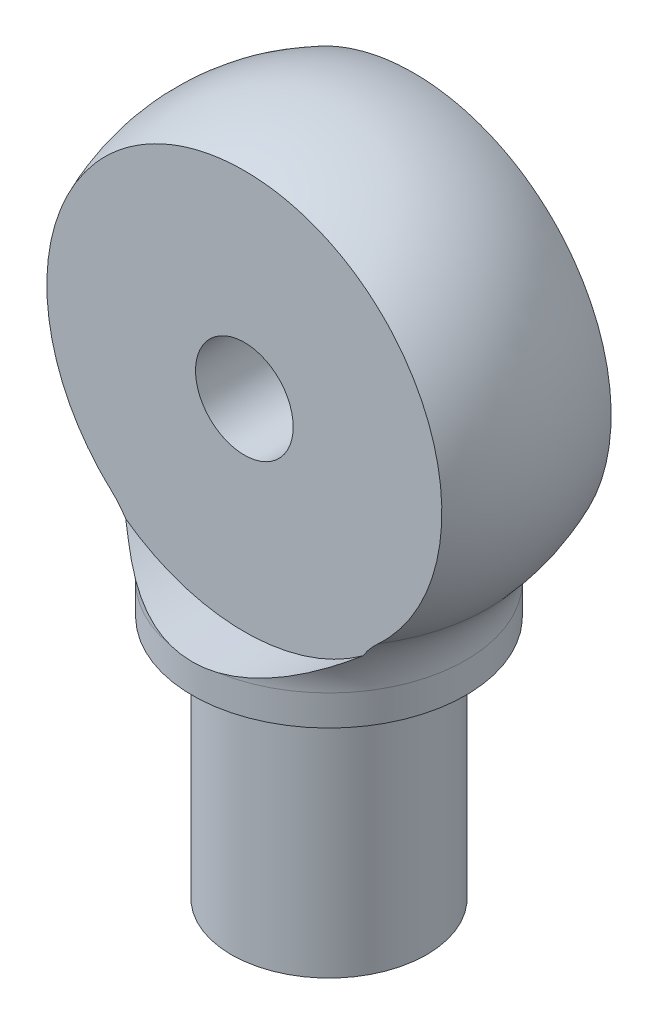
SolidWorks part; units mm, degrees
ref_plane "Front Plane" through (0, 0, 0) normal (0, 0, 1) x (1, 0, 0)
ref_plane "Top Plane" through (0, 0, 0) normal (0, 1, 0) x (1, 0, 0)
ref_plane "Right Plane" through (0, 0, 0) normal (1, 0, 0) x (0, 0, -1)
sketch "Sketch1" plane through (0, 0, 0) normal (0, 1, 0) x (1, 0, 0)
  circle A0 centre (0, 0) radius 7.62
extrude "Boss-Extrude1" add sketch "Sketch1" along normal blind 19.05
sketch "Sketch2" plane through (0, 0, 0) normal (1, 0, 0) x (0, 0, -1)
  line L0 (0, 8.382) -> (0, -8.382) construction
  line L1 (-10.668, 19.05) -> (-10.668, 24.13)
  line L2 (-10.668, 19.05) -> (0, 19.05)
  line L3 (7.62, 19.05) -> (-7.62, 19.05) construction
  line L4 (0, 19.05) -> (0, 53.8256)
  arc A0 (0, 53.8256) -> (-10.668, 24.13) centre (0, 37.0616) ccw
  dimension "D3" = 33.528
  dimension "D1" = 5.08
  dimension "D2" = 10.668
revolve "Revolve1" add sketch "Sketch2" angle 360 about L4
sketch "Sketch7" plane through (0, 0, 0) normal (0, 0, 1) x (1, 0, 0)
  line L0 (0, -8.382) -> (0, 8.382) construction
  circle A0 centre (0, 37.0616) radius 3.81
extrude "Cut-Extrude3" cut sketch "Sketch7" against normal through all both and the other way through all
ref_plane "Plane1" through (0, 0, 6.604) normal (0, 0, 1) x (1, 0, 0)
sketch "Sketch8" plane through (0, 0, 6.604) normal (0, 0, 1) x (1, 0, 0)
  circle A0 centre (0, 37.0616) radius 15.748
  dimension "D1" = 31.496
extrude "Cut-Extrude4" cut sketch "Sketch8" along normal blind 17.78
mirror "Mirror1" about plane through (0, 0, 0) normal (0, 0, 1) of "Cut-Extrude4"
fillet "Fillet1" radius 6.35 2 edges at (-10.668, 24.13, 0) (10.668, 24.13, 0)
